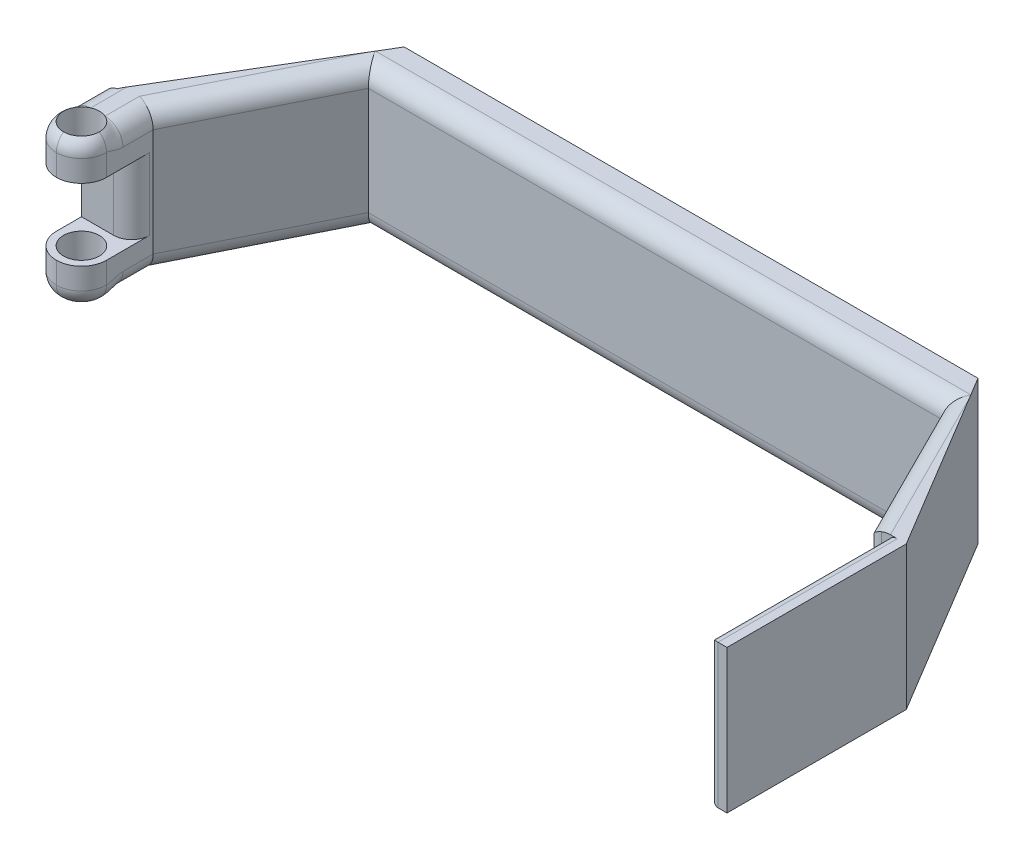
SolidWorks part; units mm, degrees
ref_plane "Front Plane" through (0, 0, 0) normal (0, 0, 1) x (1, 0, 0)
ref_plane "Top Plane" through (0, 0, 0) normal (0, 1, 0) x (1, 0, 0)
ref_plane "Right Plane" through (0, 0, 0) normal (1, 0, 0) x (0, 0, -1)
sketch "Sketch1" plane through (0, 0, 0) normal (0, 1, 0) x (1, 0, 0)
  line L0 (0, 0) -> (20, 40)
  line L1 (20, 40) -> (180, 40)
  line L2 (180, 40) -> (200, 0)
  line L3 (0, 0) -> (-10, 0)
  line L4 (-10, 0) -> (20, 50)
  line L5 (20, 50) -> (180, 50)
  line L6 (200, 0) -> (210, 0)
  line L7 (210, 0) -> (180, 50)
  dimension "D1" = 20
  dimension "D2" = 40
  dimension "D3" = 160
  dimension "D4" = 20
  dimension "D5" = 40
  dimension "D6" = 10
  dimension "D7" = 10
  dimension "D8" = 10
extrude "Boss-Extrude1" add sketch "Sketch1" along normal blind 40
sketch "Sketch2" plane through (0, 0, 0) normal (0, 0, 1) x (1, 0, 0)
  line L1 (0, 40) -> (-14, 40)
  line L2 (0, 40) -> (0, 0)
  line L3 (0, 0) -> (-14, 0)
  line L4 (-14, 40) -> (-14, 0)
  dimension "D1" = 14
extrude "Boss-Extrude2" add sketch "Sketch2" along normal blind 20
sketch "Sketch3" plane through (0, 0, 0) normal (1, 0, 0) x (0, 0, -1)
  line L0 (-20, 0) -> (-20, 40) construction
  line L1 (-20, 30) -> (-6, 30)
  line L2 (-20, 30) -> (-20, 10)
  line L3 (-20, 10) -> (-6, 10)
  line L4 (-6, 30) -> (-6, 10)
  line L5 (-20, 0) -> (0, 0) construction
  dimension "D1" = 14
  dimension "D2" = 20
  dimension "D3" = 10
extrude "Cut-Extrude2" cut sketch "Sketch3" against normal up to next
sketch "Sketch5" plane through (0, 10, 0) normal (0, 1, 0) x (1, 0, 0)
  circle A0 centre (-7, -13) radius 5
  dimension "D1" = 10
extrude "Cut-Extrude3" cut sketch "Sketch5" against normal through all and the other way through all
fillet "Fillet1" radius 7 4 edges at (-14, 5, 20) (0, 5, 20) (0, 35, 20) (-14, 35, 20)
sketch "Sketch7" plane through (0, 0, 0) normal (0, 0, 1) x (1, 0, 0)
  line L0 (200, 0) -> (210, 0) construction
  line L1 (210, 40) -> (205, 40)
  line L2 (210, 40) -> (210, 0)
  line L3 (210, 0) -> (205, 0)
  line L4 (205, 40) -> (205, 0)
extrude "Boss-Extrude3" add sketch "Sketch7" along normal blind 50
fillet "Fillet2" radius 5 12 edges at (0, 0, 6.5) (-14, 0, 6.5) (-14, 40, 6.5) (0, 40, 6.5) (0, 20, 6) (200, 20, 0) (190, 40, -20) (190, 0, -20) (100, 0, -40) (10, 0, -20) (100, 40, -40) (10, 40, -20)
fillet "Fillet3" radius 2.5 3 edges at (205, 20, 50) (205, 0, 24.4098) (205, 40, 24.4098)
